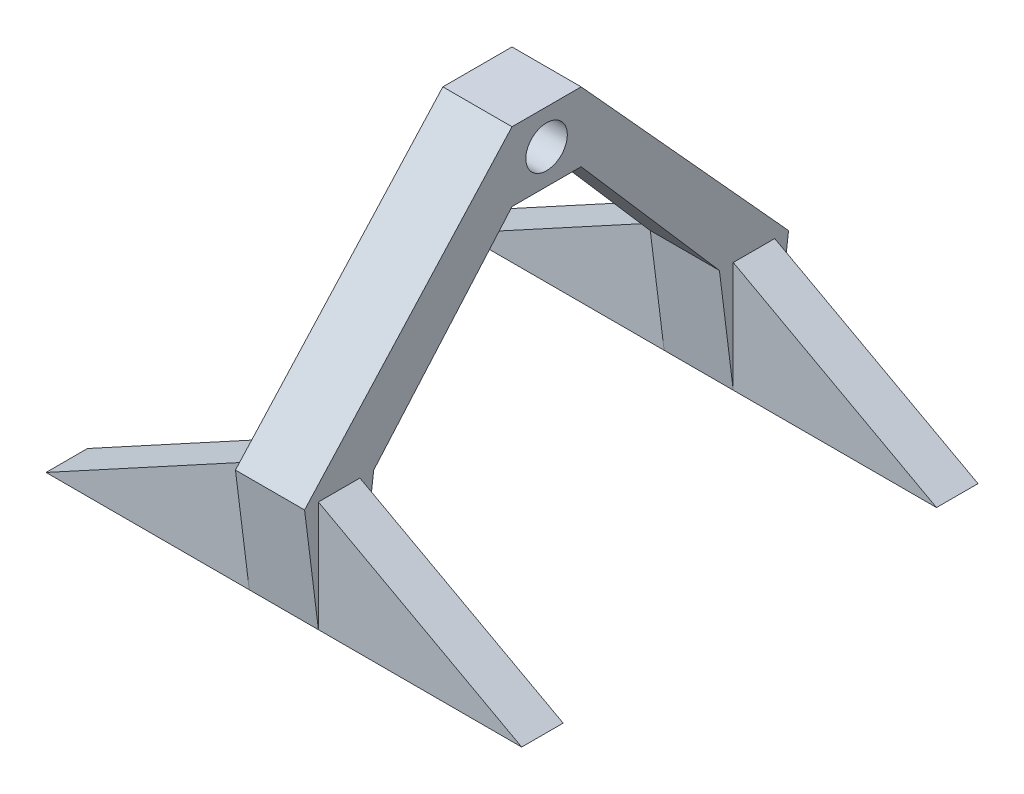
SolidWorks part; units mm, degrees
ref_plane "Front Plane" through (0, 0, 0) normal (0, 0, 1) x (1, 0, 0)
ref_plane "Top Plane" through (0, 0, 0) normal (0, 1, 0) x (1, 0, 0)
ref_plane "Right Plane" through (0, 0, 0) normal (1, 0, 0) x (0, 0, -1)
sketch "Sketch2" plane through (0, 0, 0) normal (0, 1, 0) x (1, 0, 0)
  line L1 (-86, 7.5) -> (86, 7.5)
  line L2 (-86, 7.5) -> (-86, -7.5)
  line L3 (-86, -7.5) -> (86, -7.5)
  line L4 (86, 7.5) -> (86, -7.5)
  line L5 (-86, 7.5) -> (86, -7.5) construction
  line L6 (-86, -7.5) -> (86, 7.5) construction
  line L7 (-12.5, -12.5) -> (12.5, -12.5)
  line L8 (-12.5, -12.5) -> (-12.5, 12.5)
  line L9 (-12.5, 12.5) -> (12.5, 12.5)
  line L10 (12.5, -12.5) -> (12.5, 12.5)
  line L11 (-12.5, -12.5) -> (12.5, 12.5) construction
  line L12 (-12.5, 12.5) -> (12.5, -12.5) construction
  line L13 (-86, 12.5) -> (86, 12.5)
  line L14 (-86, 12.5) -> (-86, -12.5)
  line L15 (-86, -12.5) -> (86, -12.5)
  line L16 (86, 12.5) -> (86, -12.5)
  point P0 (0, 0)
  point P6 (0, 0)
  dimension "D1" = 15
  dimension "D2" = 172
  dimension "D3" = 25
  dimension "D4" = 25
extrude "Boss-Extrude3" add sketch "Sketch2" along normal blind 40 contours L7 L10 L3 L8 | L3 L10 L1 L8 | L1 L10 L9 L8 | L3 L8 L1 L2 | L10 L3 L4 L1 region at (-49.25, 0, 0) region at (0, 0, -10) region at (0, 0, 0) region at (49.25, 0, 0) region at (0, 0, 10)
ref_plane "Plane2" through (0, 0, 75) normal (0, 0, 1) x (1, 0, 0)
ref_axis "Axis1" through (0, -2, 75) along (0, 1, 0)
sketch "Sketch6" plane through (0, 0, -7.5) normal (0, 0, -1) x (-1, 0, 0)
  line L0 (12.5, 40) -> (86, 0)
  line L1 (86, 0) -> (86, 40)
  line L2 (86, 40) -> (12.5, 40)
extrude "Cut-Extrude1" cut sketch "Sketch6" against normal up to next
mirror "Mirror1" about plane through (0, 0, 0) normal (1, 0, 0) of "Cut-Extrude1"
sketch "Sketch7" plane through (-12.5, 0, 0) normal (-1, 0, 0) x (0, 0, 1)
  line L0 (-12.5, 40) -> (-7.5, 0)
  line L1 (-7.5, 0) -> (-12.5, 0)
  line L2 (-12.5, 0) -> (-12.5, 40)
extrude "Cut-Extrude3" cut sketch "Sketch7" against normal up to next
mirror "Mirror2" about plane through (0, 0, 0) normal (0, 0, 1) of "Cut-Extrude3"
sketch "Sketch5" plane through (0, 0, 0) normal (1, 0, 0) x (0, 0, -1)
  line L0 (-75, -2) -> (-75, 143.3535) construction
  line L1 (-62.5, 122.5) -> (-87.5, 122.5)
  line L2 (-62.5, 122.5) -> (-62.5, 97.5)
  line L3 (-62.5, 97.5) -> (-87.5, 97.5)
  line L4 (-87.5, 122.5) -> (-87.5, 97.5)
  line L5 (-62.5, 122.5) -> (-87.5, 97.5) construction
  line L6 (-62.5, 97.5) -> (-87.5, 122.5) construction
  circle A0 centre (-75, 110) radius 7.5
  point P0 (-75, 110)
  dimension "D3" = 15
  dimension "D1" = 25
  dimension "D2" = 25
  dimension "D4" = 110
extrude "Boss-Extrude4" add sketch "Sketch5" along normal blind 12.5 and the other way blind 12.5 separate body
sketch "Sketch8" plane through (0, 0, 0) normal (1, 0, 0) x (0, 0, -1)
  line L0 (-62.5, 97.5) -> (-12.5, 40)
  line L1 (-62.5, 122.5) -> (12.5, 40)
  line L2 (12.5, 40) -> (-12.5, 40)
  line L3 (-62.5, 122.5) -> (-62.5, 97.5)
extrude "Boss-Extrude5" add sketch "Sketch8" along normal up to surface (12.5 mm away) and the other way up to surface (12.5 mm away) up to face at (12.5, 110, 75) other way up to face at (-12.5, 110, 67.5)
mirror "Mirror13" about plane through (0, 0, 75) normal (0, 0, 1) of bodies 110
